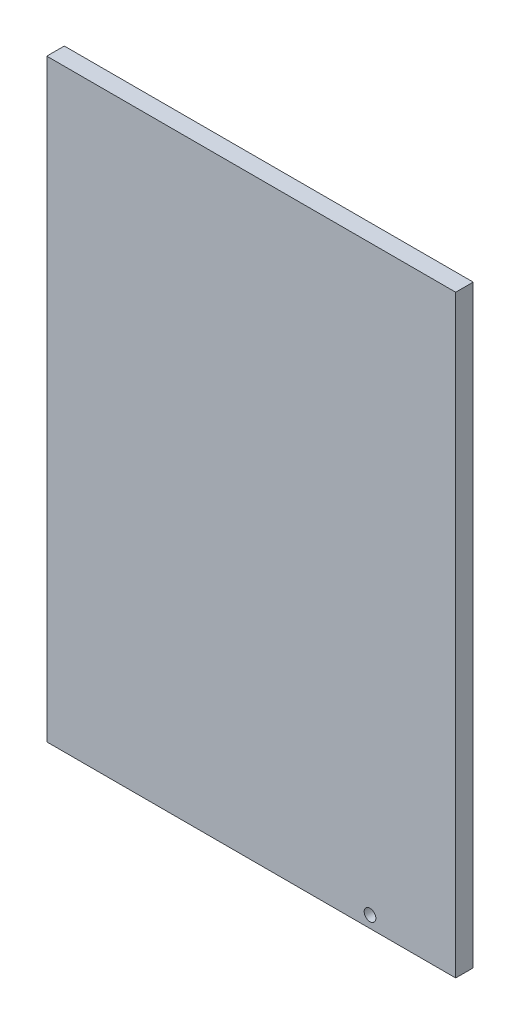
SolidWorks part; units mm, degrees
ref_plane "Front Plane" through (0, 0, 0) normal (0, 0, 1) x (1, 0, 0)
ref_plane "Top Plane" through (0, 0, 0) normal (0, 1, 0) x (1, 0, 0)
ref_plane "Right Plane" through (0, 0, 0) normal (1, 0, 0) x (0, 0, -1)
sketch "Sketch1" plane through (0, 0, 0) normal (0, 0, 1) x (1, 0, 0)
  line L1 (-105, -152.5) -> (105, -152.5)
  line L2 (-105, -152.5) -> (-105, 152.5)
  line L3 (-105, 152.5) -> (105, 152.5)
  line L4 (105, -152.5) -> (105, 152.5)
  line L5 (-105, -152.5) -> (105, 152.5) construction
  line L6 (-105, 152.5) -> (105, -152.5) construction
  point P0 (0, 0)
  dimension "D1" = 210
  dimension "D2" = 305
extrude "Boss-Extrude1" add sketch "Sketch1" along normal blind 9
sketch "Sketch2" plane through (0, 0, 9) normal (0, 0, 1) x (1, 0, 0)
  line L0 (105, -152.5) -> (105, 152.5) construction
  line L1 (-105, -152.5) -> (105, -152.5) construction
  circle A0 centre (61, -146.5) radius 3
  dimension "D1" = 6
  dimension "D2" = 44
  dimension "D3" = 6
extrude "Cut-Extrude1" cut sketch "Sketch2" against normal through all
sketch "Sketch3" [suppressed] plane through (0, 0, 0) normal (0, 0, -1) x (-1, 0, 0)
  line L0 (-120.2594, -152.5) -> (119.7406, -152.5) construction
  line L2 (-90.2594, -139.5) -> (-30.2594, -139.5) construction
  line L3 (-30.2594, -139.5) -> (29.7406, -139.5) construction
  line L4 (29.7406, -139.5) -> (89.7406, -139.5) construction
  circle A0 centre (-90.2594, -139.5) radius 4.75
  circle A1 centre (-30.2594, -139.5) radius 5.5875
  circle A2 centre (29.7406, -139.5) radius 4.75
  circle A3 centre (89.7406, -139.5) radius 5.5875
  point P3 (-0.2594, -152.5)
  dimension "D2" = 9.5
  dimension "D7" = 11.175
  dimension "D1" = 240
  dimension "D3" = 13
  dimension "D4" = 30
  dimension "D5" = 60
  dimension "D6" = 60
  dimension "60" = 60
extrude "Cut-Extrude2" [suppressed] cut sketch "Sketch3" against normal through all
equation "\"PCLength\"= 320mm'Length across I/O from PS to GPU"
equation "\"PCWidth\"= 242mm'Distance of longest part parallel to GPU(ussually GPU)"
equation "\"PCHeight\"= 172mm'Tallest point with mobo laying flat"
equation "\"WallThickness\"= 9mm'Thickness of each outer tank wall"
equation "\"ThermoBarrierThickness\"= 3mm'Thickness of barrier between hot side and cold side"
equation "\"HotSideGap\"= 35mm'Space in the hot side for a pump"
equation "\"PCClearance\"= 30mm'Clearance from top of tank to top of PC"
equation "\"RadiatorHeight\"= 275mm'Final Height from ground of radiators"
equation "\"D1@Sketch1\"=\"PCHeight\" + \"ThermoBarrierThickness\" + \"HotSideGap\""
equation "\"D2@Sketch1\"=\"RadiatorHeight\" + \"PCClearance\""
equation "\"D1@Boss-Extrude1\"=\"WallThickness\""
equation "\"D2@Sketch2\"=\"HotSideGap\" + \"ThermoBarrierThickness\" + 6"
